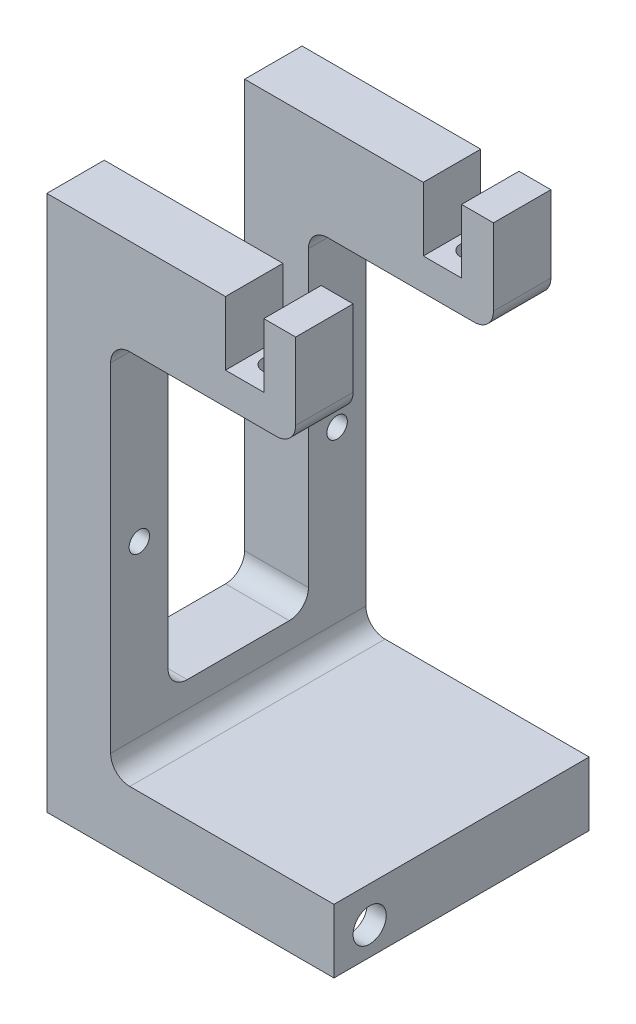
SolidWorks part; units mm, degrees
ref_plane "Front Plane" through (0, 0, 0) normal (0, 0, 1) x (1, 0, 0)
ref_plane "Top Plane" through (0, 0, 0) normal (0, 1, 0) x (1, 0, 0)
ref_plane "Right Plane" through (0, 0, 0) normal (1, 0, 0) x (0, 0, -1)
sketch "Sketch1" plane through (0, 0, 0) normal (0, 0, 1) x (1, 0, 0)
  line L0 (10, 10) -> (45, 10)
  line L1 (0, 0) -> (45, 0)
  line L2 (0, 0) -> (0, 84)
  line L3 (0, 84) -> (28, 84)
  line L5 (10, 10) -> (10, 69)
  line L6 (10, 69) -> (39, 69)
  line L8 (45, 10) -> (45, 0)
  line L19 (39, 84) -> (39, 69)
  line L20 (28, 84) -> (34, 84) construction
  line L21 (28, 84) -> (34, 84) construction
  line L22 (28, 84) -> (28, 74)
  line L23 (28, 74) -> (34, 74)
  line L24 (34, 84) -> (34, 74)
  line L25 (34, 84) -> (39, 84)
  dimension "D2" = 84
  dimension "D3" = 39
  dimension "D4" = 45
  dimension "D5" = 5
  dimension "D6" = 6
  dimension "D7" = 10
  dimension "D1" = 10
  dimension "D8" = 15
  dimension "D9" = 10
extrude "Boss-Extrude1" add sketch "Sketch1" along normal blind 40
sketch "Sketch2" plane through (0, 0, 0) normal (-1, 0, 0) x (0, 0, 1)
  line L0 (40, 84) -> (0, 84) construction
  line L1 (9, 84) -> (31, 84)
  line L2 (9, 84) -> (9, 17)
  line L3 (9, 17) -> (31, 17)
  line L4 (31, 84) -> (31, 17)
  line L5 (40, 0) -> (0, 0) construction
  point P9 (20, 0)
  point P10 (20, 17)
  dimension "D1" = 17
  dimension "D2" = 22
extrude "Cut-Extrude1" cut sketch "Sketch2" against normal through all
sketch "Sketch4" plane through (0, 74, 0) normal (0, 1, 0) x (1, 0, 0)
  line L0 (31, -31) -> (31, -40) construction
  line L1 (34, -31) -> (28, -31) construction
  line L2 (34, -40) -> (28, -40) construction
  line L3 (0, -20) -> (45, -20) construction
  line L4 (0, -9) -> (0, -31) construction
  line L5 (45, -40) -> (45, 0) construction
  circle A0 centre (31, -35.5) radius 1.7
  circle A1 centre (31, -4.5) radius 1.7
  dimension "D1" = 3.4
extrude "Cut-Extrude2" cut sketch "Sketch4" against normal up to next
sketch "Sketch7" plane through (45, 0, 0) normal (1, 0, 0) x (0, 0, -1)
  line L1 (-40, 0) -> (-40, 10) construction
  line L2 (-40, 10) -> (0, 10) construction
  circle A0 centre (-34.4, 4.4) radius 2.6
  dimension "D1" = 5.2
  dimension "D2" = 5.6
  dimension "D3" = 5.6
extrude "Cut-Extrude3" cut sketch "Sketch7" against normal blind 10
fillet "Fillet1" radius 3 3 edges at (10, 10, 20) (5, 17, 31) (5, 17, 9)
fillet "Fillet2" radius 3 4 edges at (39, 69, 4.5) (39, 69, 35.5) (10, 69, 35.5) (10, 69, 4.5)
sketch "Sketch8" plane through (0, 0, 0) normal (0, -1, 0) x (1, 0, 0)
  line L8 (3, 3) -> (42, 3)
  line L9 (42, 3) -> (42, 37)
  line L10 (42, 37) -> (3, 37)
  line L11 (3, 37) -> (3, 3)
  line L12 (3, 3) -> (42, 3)
  line L13 (42, 3) -> (42, 37)
  line L14 (42, 37) -> (3, 37)
  line L15 (3, 37) -> (3, 3)
  dimension "D1" = 3
extrude "Cut-Extrude4" cut sketch "Sketch8" against normal blind 7
sketch "Sketch9" plane through (10, 0, 0) normal (1, 0, 0) x (0, 0, -1)
  line L0 (-4.5, 66) -> (-4.5, 13) construction
  line L1 (0, 66) -> (-9, 66) construction
  line L2 (-40, 13) -> (0, 13) construction
  line L3 (-20, 17) -> (-20, 82.5748) construction
  line L4 (-12, 17) -> (-28, 17) construction
  circle A0 centre (-4.5, 39.5) radius 1.6
  circle A1 centre (-35.5, 39.5) radius 1.6
  dimension "D1" = 3.2
extrude "Cut-Extrude5" cut sketch "Sketch9" against normal up to next
